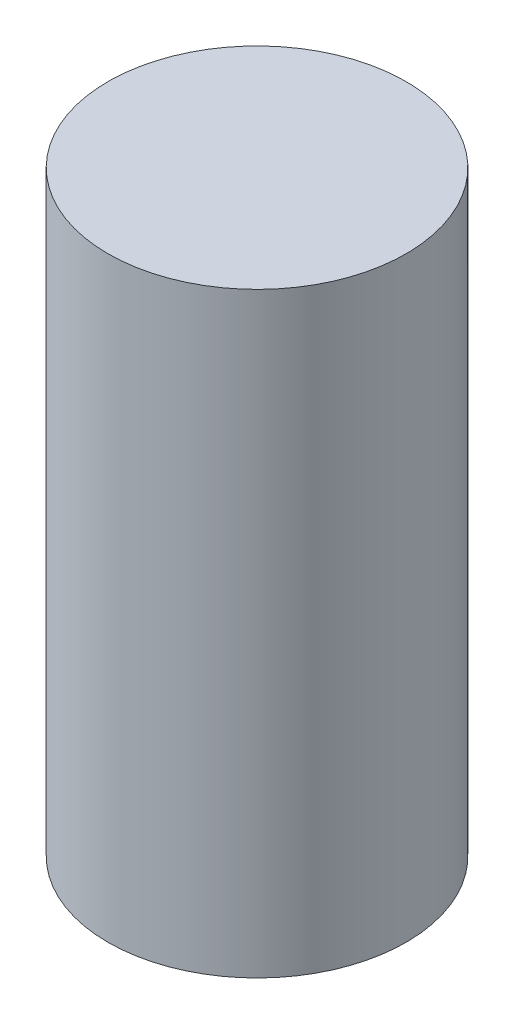
SolidWorks part; units mm, degrees
ref_plane "前视基准面" through (0, 0, 0) normal (0, 0, 1) x (1, 0, 0)
ref_plane "上视基准面" through (0, 0, 0) normal (0, 1, 0) x (1, 0, 0)
ref_plane "右视基准面" through (0, 0, 0) normal (1, 0, 0) x (0, 0, -1)
other "Configuration Table"
sketch "草图1" plane through (0, 0, 0) normal (0, 1, 0) x (1, 0, 0)
  circle A0 centre (0, 0) radius 30
extrude "凸台-拉伸1" add sketch "草图1" along normal blind 120
